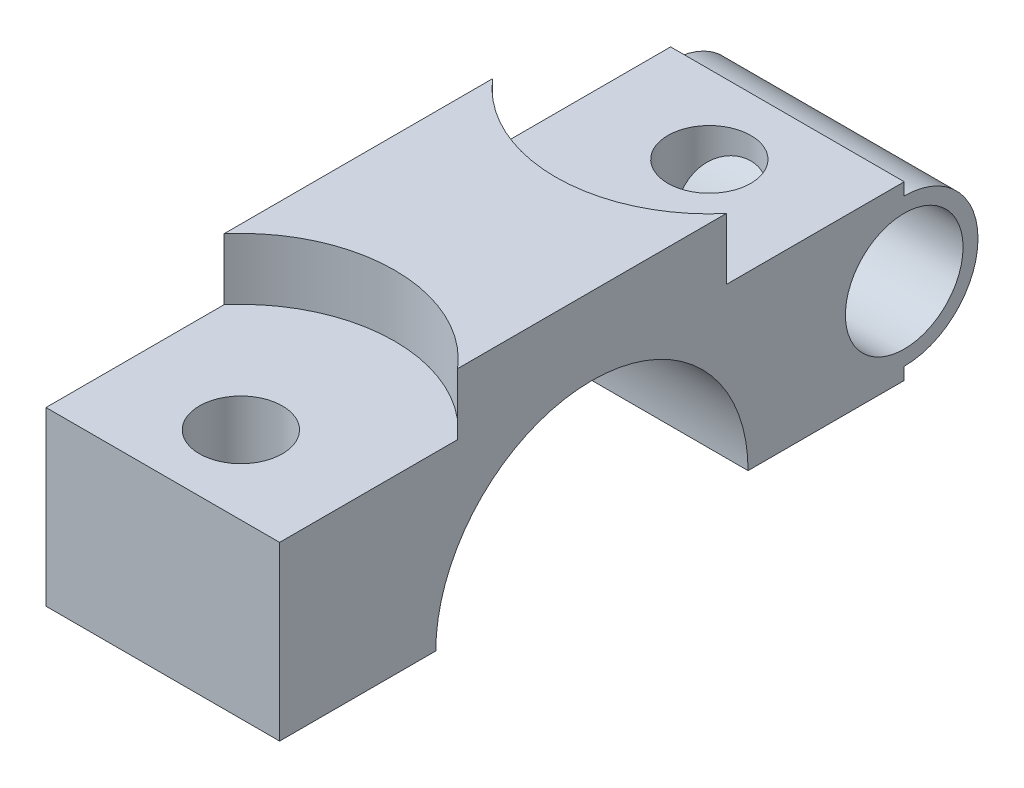
SolidWorks part; units mm, degrees
ref_plane "Front Plane" through (0, 0, 0) normal (0, 0, 1) x (1, 0, 0)
ref_plane "Top Plane" through (0, 0, 0) normal (0, 1, 0) x (1, 0, 0)
ref_plane "Right Plane" through (0, 0, 0) normal (1, 0, 0) x (0, 0, -1)
sketch "Sketch1" plane through (0, 0, 0) normal (1, 0, 0) x (0, 0, -1)
  line L0 (12.7, 0) -> (25.4, 0)
  line L1 (-25.4, 19) -> (25.4, 19)
  line L2 (-25.4, 19) -> (-25.4, 0)
  line L3 (-25.4, 0) -> (-12.7, 0)
  line L4 (25.4, 19) -> (25.4, 0)
  arc A0 (-12.7, 0) -> (12.7, 0) centre (0, 0) cw
  dimension "D3" = 12.7
  dimension "D1" = 50.8
  dimension "D2" = 19
  dimension "D4" = 25.4
extrude "Boss-Extrude1" add sketch "Sketch1" along normal mid plane 19
sketch "Sketch2" plane through (0, 0, 0) normal (0, -1, 0) x (1, 0, 0)
  line L0 (-9.5, 19.05) -> (9.5, 19.05) construction
  line L1 (-9.5, 25.4) -> (-9.5, 12.7) construction
  line L2 (9.5, 25.4) -> (9.5, 12.7) construction
  line L3 (-9.5, -19.05) -> (9.5, -19.05) construction
  line L4 (-9.5, -12.7) -> (-9.5, -25.4) construction
  line L5 (9.5, -12.7) -> (9.5, -25.4) construction
  point P12 (0, 19.05)
  point P13 (0, -19.05)
hole_wizard "CBORE for M12 Hex Head Bolt3" positions "Sketch4" profile "Sketch5" counterbore size "M12" standard "ISO" end condition through all
sketch "Sketch4" plane through (0, 19, 0) normal (0, 1, 0) x (1, 0, 0)
  point P0 (0, 19.05)
  point P3 (0, -19.05)
sketch "Sketch5" plane through (0, 19, -19.05) normal (1, 0, 0) x (0, 0, 1)
  line L0 (0, 0) -> (0, 19)
  line L1 (0, 19) -> (3.375, 19)
  line L3 (3.375, 19) -> (3.375, 5)
  line L4 (3.375, 5) -> (12.5, 5)
  line L5 (12.5, 5) -> (12.5, 0)
  line L7 (12.5, 0) -> (0, 0)
  line L11 (0, -6.35) -> (0, 107.95) construction
  dimension "Thru Hole Dia." = 6.75
  dimension "Thru Hole Depth" = 19
  dimension "C'Bore Dia." = 25
  dimension "C'Bore Depth" = 5
sketch "Sketch6" plane through (9.5, 0, 0) normal (1, 0, 0) x (0, 0, -1)
  line L0 (25.4, 0) -> (25.4, 14) construction
  circle A0 centre (25.4, 7) radius 6
  circle A1 centre (25.4, 7) radius 4.785
  point P5 (0, 0)
  point P6 (25.4, 7)
  line M12 (25.4, 0) -> (25.4, 14)
  dimension "D1" = 12
  dimension "D2" = 9.57
extrude "Cut-Extrude1" cut sketch "Sketch6" against normal blind 19 contours A1 M12 | A1 M12 region at (9.5, 7, -23.3692) region at (9.5, 7, -27.4308)
extrude "Boss-Extrude2" add sketch "Sketch6<3>" against normal blind 19
sketch "Sketch6<3>" plane through (9.5, 0, 0) normal (1, 0, 0) x (0, 0, -1) same geometry as "Sketch6"
